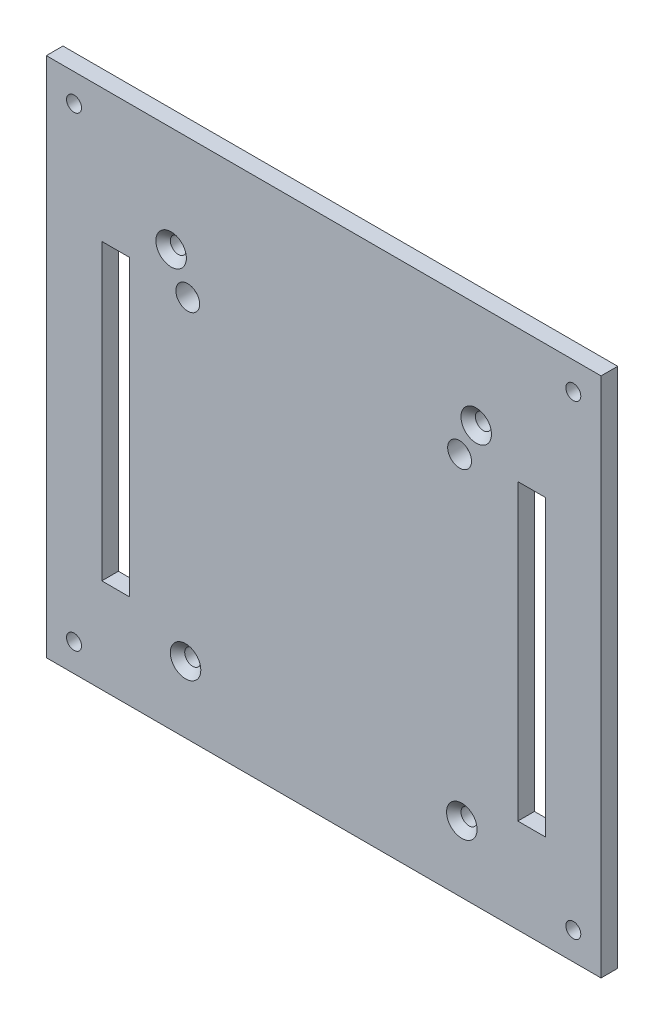
SolidWorks part; units mm, degrees
ref_plane "Alzado" through (0, 0, 0) normal (0, 0, 1) x (1, 0, 0)
ref_plane "Planta" through (0, 0, 0) normal (0, 1, 0) x (1, 0, 0)
ref_plane "Vista lateral" through (0, 0, 0) normal (1, 0, 0) x (0, 0, -1)
sketch "Croquis1" plane through (0, 0, 0) normal (0, 0, 1) x (1, 0, 0)
  line L1 (0, 82) -> (100, 82)
  line L2 (0, 82) -> (0, 0)
  line L3 (0, 0) -> (100, 0)
  line L4 (100, 82) -> (100, 0)
  line L5 (0, 82) -> (100, 82)
  line L9 (0, 0) -> (100, 0)
  dimension "D1" = 100
  dimension "D2" = 82
extrude "Saliente-Extruir1" add sketch "Croquis1" along normal blind 3 contours L1 | L3 | L2 L3 L4 L1 region at (50, 41, 0)
sketch "Croquis3" plane through (0, 0, 3) normal (0, 0, 1) x (1, 0, 0)
  line L0 (50, 82) -> (50, 0) construction
  line L3 (0, 6) -> (100, 6) construction
  line L4 (100, 69) -> (0, 69) construction
  line L5 (22.5, 0) -> (22.5, 82) construction
  line L6 (25.1, 0) -> (25.1, 82) construction
  line L7 (74.9, 0) -> (74.9, 82) construction
  line L8 (77.5, 0) -> (77.5, 82) construction
  line L15 (0, 82) -> (100, 82) construction
  line L16 (0, 0) -> (100, 0) construction
  line L17 (0, 82) -> (0, 0) construction
  line L18 (100, 82) -> (100, 0) construction
  dimension "D1" = 24.9
  dimension "D2" = 24.9
  dimension "D3" = 27.5
  dimension "D4" = 27.5
  dimension "D5" = 6
  dimension "D6" = 13
hole_wizard "Avellanado para tornillo con cabeza plana avellanada de M2.51" positions "Croquis3D1" profile "Croquis4" countersink size "M2.5" standard "ISO" end condition through all
sketch3d "Croquis3D1"
  line L0 (100, 69, 3) -> (0, 69, 3) construction
  line L1 (22.5, 0, 3) -> (22.5, 82, 3) construction
  line L2 (77.5, 0, 3) -> (77.5, 82, 3) construction
  line L3 (0, 6, 3) -> (100, 6, 3) construction
  line L4 (74.9, 0, 3) -> (74.9, 82, 3) construction
  line L5 (25.1, 0, 3) -> (25.1, 82, 3) construction
  point P0 (22.5, 69, 3)
  point P6 (77.5, 69, 3)
  point P10 (74.9, 6, 3)
  point P16 (25.1, 6, 3)
sketch "Croquis4" plane through (22.5, 69, 3) normal (1, 0, 0) x (0, -1, 0)
  line L0 (0, 0) -> (0, 3)
  line L1 (0, 3) -> (1.45, 3)
  line L2 (1.45, 3) -> (1.45, 1.3)
  line L3 (1.45, 1.3) -> (2.75, 0)
  line L5 (2.75, 0) -> (0, 0)
  line L6 (-1.45, 1.3) -> (-2.75, 0) construction
  line L11 (0, -6.35) -> (0, 107.95) construction
  dimension "Diámetro de taladro hasta el siguiente" = 2.9
  dimension "Profundidad de taladro hasta el siguiente" = 3
  dimension "Diámetro de avellanado cercano" = 5.5
  dimension "Ángulo de avellanado cercano" = 90
sketch "Croquis6" plane through (0, 0, 3) normal (0, 0, 1) x (1, 0, 0)
  line L1 (10, 64) -> (15, 64)
  line L2 (10, 64) -> (10, 11)
  line L3 (10, 11) -> (15, 11)
  line L4 (15, 64) -> (15, 11)
  line L5 (100, 69) -> (0, 69) construction
  line L6 (0, 6) -> (100, 6) construction
  line L7 (50, 82) -> (50, 0) construction
  line L8 (0, 82) -> (100, 82) construction
  line L9 (90, 11) -> (85, 11)
  line L10 (90, 64) -> (90, 11)
  line L11 (85, 64) -> (85, 11)
  line L12 (0, 82) -> (0, 0) construction
  line L13 (90, 64) -> (85, 64)
  dimension "D1" = 5
  dimension "D2" = 5
  dimension "D3" = 5
  dimension "D8" = 10
extrude "Cortar-Extruir1" cut sketch "Croquis6" against normal up to next
sketch "Croquis7" plane through (0, 82, 0) normal (0, 1, 0) x (1, 0, 0)
  line L1 (0, 0) -> (100, 0)
  line L2 (0, 0) -> (0, -3)
  line L3 (0, -3) -> (100, -3)
  line L4 (100, 0) -> (100, -3)
extrude "Saliente-Extruir2" add sketch "Croquis7" along normal blind 6
sketch "Croquis8" plane through (0, 0, 0) normal (0, -1, 0) x (1, 0, 0)
  line L1 (0, 3) -> (100, 3)
  line L2 (0, 3) -> (0, 0)
  line L3 (0, 0) -> (100, 0)
  line L4 (100, 3) -> (100, 0)
extrude "Saliente-Extruir3" add sketch "Croquis8" along normal blind 6
sketch "Croquis9" plane through (0, 0, 3) normal (0, 0, 1) x (1, 0, 0)
  line L1 (100, 88) -> (100, -6) construction
  line L3 (100, -6) -> (0, -6) construction
  circle A0 centre (87.5, 4) radius 2.5
  dimension "D1" = 5
  dimension "D3" = 10
  dimension "D2" = 12.5
sketch "Croquis11" plane through (0, 0, 3) normal (0, 0, 1) x (1, 0, 0)
  line L0 (0, 83) -> (100, 83) construction
  line L1 (0, 88) -> (0, -6) construction
  line L2 (100, 88) -> (100, -6) construction
  line L3 (5, 88) -> (5, -6) construction
  line L4 (0, 88) -> (100, 88) construction
  line L5 (100, -6) -> (0, -6) construction
  line L6 (95, 88) -> (95, -6) construction
  line L7 (0, -1) -> (100, -1) construction
  dimension "D1" = 5
  dimension "D2" = 5
  dimension "D3" = 5
  dimension "D4" = 5
hole_wizard "Taladro de margen para M2.51" positions "Croquis3D2" profile "Croquis12" hole size "M2.5" standard "ISO" end condition through all
sketch3d "Croquis3D2"
  line L0 (0, 83, 3) -> (100, 83, 3) construction
  line L1 (5, 88, 3) -> (5, -6, 3) construction
  line L2 (0, -1, 3) -> (100, -1, 3) construction
  line L3 (95, 88, 3) -> (95, -6, 3) construction
  point P0 (5, 83, 3)
  point P6 (5, -1, 3)
  point P10 (95, -1, 3)
  point P14 (95, 83, 3)
sketch "Croquis12" plane through (5, 83, 3) normal (1, 0, 0) x (0, -1, 0)
  line L0 (0, 0) -> (0, 3)
  line L1 (0, 3) -> (1.35, 3)
  line L2 (1.35, 3) -> (1.35, 0)
  line L5 (1.35, 0) -> (0, 0)
  line L11 (0, -6.35) -> (0, 107.95) construction
  dimension "Diámetro de taladro hasta el siguiente" = 2.7
  dimension "Profundidad de taladro hasta el siguiente" = 3
sketch "Croquis13" plane through (0, 0, 3) normal (0, 0, 1) x (1, 0, 0)
  line L0 (25.5, 88) -> (25.5, -6) construction
  line L1 (100, -6) -> (0, -6) construction
  line L2 (74.5, 88) -> (74.5, -6) construction
  line L3 (50, 88) -> (50, -6) construction
  line L4 (0, 88) -> (0, -6) construction
  line L5 (100, 88) -> (100, -6) construction
  line L6 (0, 88) -> (100, 88) construction
  line L7 (0, 63) -> (100, 63) construction
  dimension "D1" = 24.5
  dimension "D2" = 49
  dimension "D3" = 25
hole_wizard "Taladro de margen para M41" positions "Croquis3D3" profile "Croquis14" hole size "M4" standard "ISO" end condition through all
sketch3d "Croquis3D3"
  line L0 (25.5, 88, 3) -> (25.5, -6, 3) construction
  line L2 (74.5, 88, 3) -> (74.5, -6, 3) construction
  line L3 (0, 63, 3) -> (100, 63, 3) construction
  point P11 (25.5, 63, 3)
  point P15 (74.5, 63, 3)
sketch "Croquis14" plane through (25.5, 63, 3) normal (1, 0, 0) x (0, -1, 0)
  line L0 (0, 0) -> (0, 3)
  line L1 (0, 3) -> (2.15, 3)
  line L2 (2.15, 3) -> (2.15, 0)
  line L5 (2.15, 0) -> (0, 0)
  line L11 (0, -6.35) -> (0, 107.95) construction
  dimension "Diámetro de taladro hasta el siguiente" = 4.3
  dimension "Profundidad de taladro hasta el siguiente" = 3
